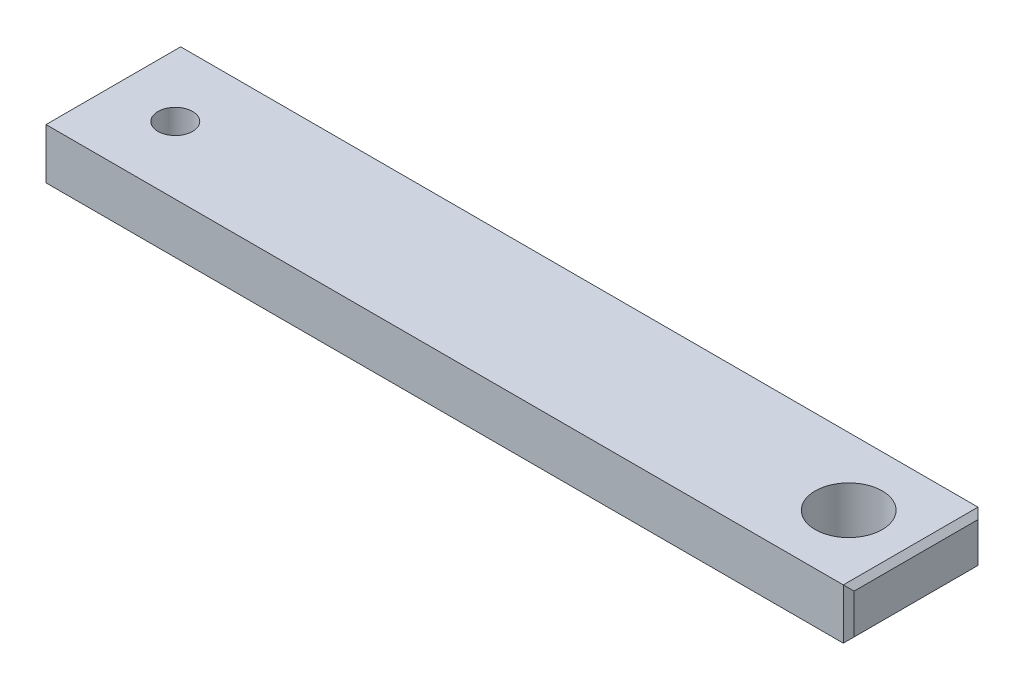
SolidWorks part; units mm, degrees
material "6061-T6 (SS)"
ref_plane "Front Plane" through (0, 0, 0) normal (0, 0, 1) x (1, 0, 0)
ref_plane "Top Plane" through (0, 0, 0) normal (0, 1, 0) x (1, 0, 0)
ref_plane "Right Plane" through (0, 0, 0) normal (1, 0, 0) x (0, 0, -1)
sketch "Sketch1" plane through (0, 0, 0) normal (0, 1, 0) x (1, 0, 0)
  line L0 (-63.5, 0) -> (0, 0) construction
  line L1 (-63.5, 6.35) -> (0, 6.35)
  line L2 (-63.5, -6.35) -> (0, -6.35)
  line L4 (-69.85, 6.35) -> (6.35, 6.35)
  line L5 (-69.85, 6.35) -> (-69.85, -6.35)
  line L6 (-69.85, -6.35) -> (6.35, -6.35)
  line L7 (6.35, 6.35) -> (6.35, -6.35)
  arc A0 (-63.5, 6.35) -> (-63.5, -6.35) centre (-63.5, 0) ccw
  arc A1 (0, -6.35) -> (0, 6.35) centre (0, 0) ccw
  point P2 (-31.75, 0)
  point P9 (-69.85, 0)
  point P10 (6.35, 0)
  dimension "D2" = 76.2
  dimension "D1" = 12.7
extrude "Boss-Extrude2" add sketch "Sketch1" along normal blind 4.7625
sketch "Sketch2" plane through (0, 4.7625, 0) normal (0, 1, 0) x (1, 0, 0)
  line L0 (6.35, 6.35) -> (6.35, -6.35) construction
  line L5 (0, 6.35) -> (0, -6.35)
  line L6 (-69.85, -6.35) -> (6.35, -6.35) construction
  line L7 (-69.85, 6.35) -> (6.35, 6.35) construction
  circle A0 centre (0, 0) radius 3.1623
  dimension "D1" = 6.3246
  dimension "D2" = 6.35
hole_wizard "#4 Clearance Hole1" positions "Sketch3" profile "Sketch4" hole size "#4" standard "ANSI Inch" end condition through all
sketch "Sketch3" plane through (0, 4.7625, 0) normal (0, 1, 0) x (1, 0, 0)
  line L0 (-63.5, 6.35) -> (-63.5, -6.35)
  line L1 (-69.85, 6.35) -> (6.35, 6.35) construction
  line L2 (-69.85, -6.35) -> (6.35, -6.35) construction
  line L4 (-69.85, 6.35) -> (-69.85, -6.35) construction
  point P0 (-63.5, 0)
  dimension "D1" = 6.35
sketch "Sketch4" plane through (-63.5, 4.7625, 0) normal (1, 0, 0) x (0, 0, 1)
  line L0 (0, 0) -> (0, 4.7625)
  line L1 (0, 4.7625) -> (1.6319, 4.7625)
  line L2 (1.6319, 4.7625) -> (1.6319, 0)
  line L5 (1.6319, 0) -> (0, 0)
  line L11 (0, -6.35) -> (0, 107.95) construction
  dimension "Thru Hole Dia." = 3.2639
  dimension "Thru Hole Depth" = 4.7625
extrude "Cut-Extrude1" cut sketch "Sketch2" against normal through all contours L5 A0 | L5 A0 region at (1.3421, 4.7625, 0) region at (-1.3421, 4.7625, 0)
chamfer "Chamfer1" distance 0.508 angle 45 8 edges at (-69.85, 2.3813, -6.35) (-69.85, 4.7625, 0) (-69.85, 2.3813, 6.35) (-69.85, 0, 0) (6.35, 2.3813, 6.35) (6.35, 4.7625, 0) (6.35, 2.3813, -6.35) (6.35, 0, 0)
